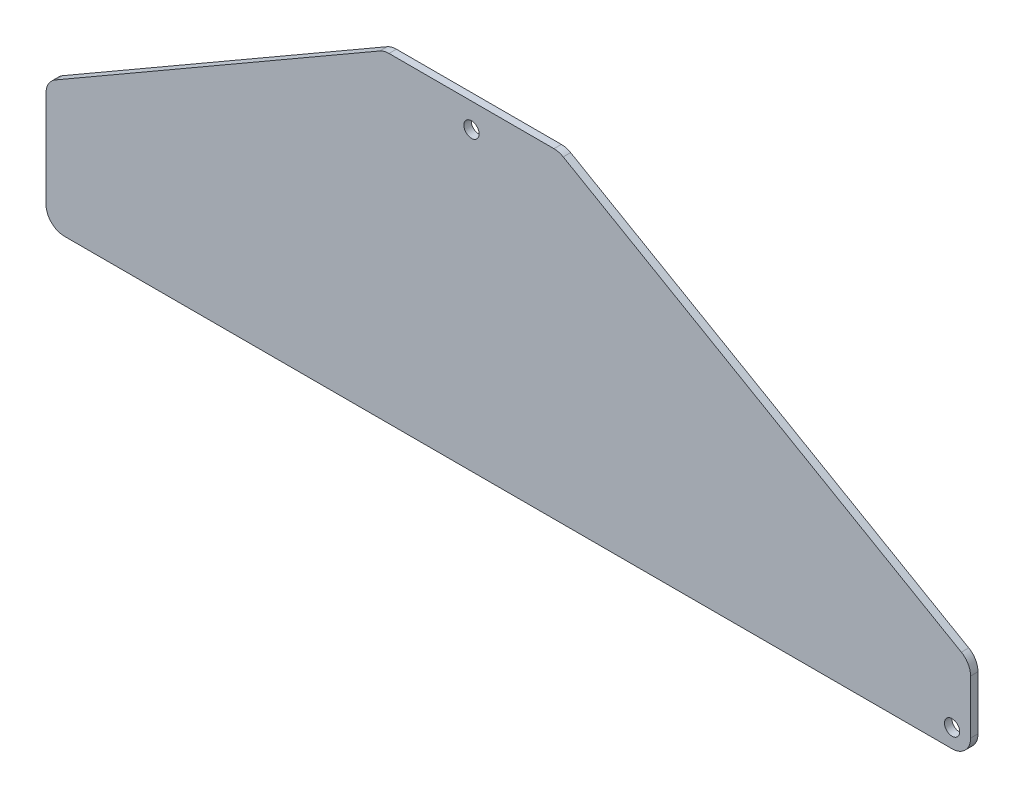
SolidWorks part; units mm, degrees
ref_plane "Front Plane" through (0, 0, 0) normal (0, 0, 1) x (1, 0, 0)
ref_plane "Top Plane" through (0, 0, 0) normal (0, 1, 0) x (1, 0, 0)
ref_plane "Right Plane" through (0, 0, 0) normal (1, 0, 0) x (0, 0, -1)
sketch "Sketch1" plane through (0, 0, 0) normal (0, 0, 1) x (1, 0, 0)
  line L0 (-92, 56) -> (107.923, 56)
  line L1 (0, 144.3376) -> (-125, 72.1688) construction
  line L2 (-125, 72.1688) -> (-125, -72.1688) construction
  line L3 (-125, -72.1688) -> (0, -144.3376) construction
  line L4 (0, -144.3376) -> (125, -72.1688) construction
  line L5 (125, -72.1688) -> (125, 72.1688) construction
  line L6 (125, 72.1688) -> (0, 144.3376) construction
  line L7 (107.923, 56) -> (107.923, 73.9453)
  line L8 (107.923, 73.9453) -> (18.909, 125.3376)
  line L9 (18.909, 125.3376) -> (-18.909, 125.3376)
  line L10 (-18.909, 125.3376) -> (-92, 83.1384)
  line L11 (-92, 83.1384) -> (-92, 56)
  line L12 (0, 0) -> (103.923, 60) construction
  line L13 (0, 0) -> (0, 120) construction
  line L14 (103.923, 60) -> (107.923, 60) construction
  line L15 (103.923, 60) -> (103.923, 56) construction
  line L21 (-125, 54.3376) -> (125, 54.3376) construction
  line L27 (-97, 54.3376) -> (-97, 88.3346) construction
  circle A0 centre (0, 0) radius 125 construction
  dimension "D1" = 250
  dimension "D2" = 7
  dimension "D3" = 7
  dimension "D4" = 120
  dimension "D5" = 97
  dimension "D6" = 4
  dimension "D7" = 19
  dimension "D8" = 90
  dimension "D11" = 5
extrude "Boss-Extrude1" add sketch "Sketch1" along normal blind 1.6
sketch "Sketch2" plane through (0, 0, 1.6) normal (0, 0, 1) x (1, 0, 0)
  line L0 (0, 0) -> (0, 120) construction
  line L1 (0, 0) -> (103.923, 60) construction
  line L2 (103.923, 60) -> (-87.522, 60) construction
  circle A0 centre (0, 120) radius 1.65
  circle A1 centre (103.923, 60) radius 1.65
  circle A2 centre (-87.522, 60) radius 1.65
  dimension "D2" = 3.3
  dimension "D1" = 120
  dimension "D3" = 60
extrude "Cut-Extrude1" cut sketch "Sketch2" against normal through all contours A0 | A1
fillet "Fillet1" radius 4 6 edges at (-18.909, 125.3376, 0.8) (18.909, 125.3376, 0.8) (107.923, 73.9453, 0.8) (107.923, 56, 0.8) (-92, 56, 0.8) (-92, 83.1384, 0.8)
